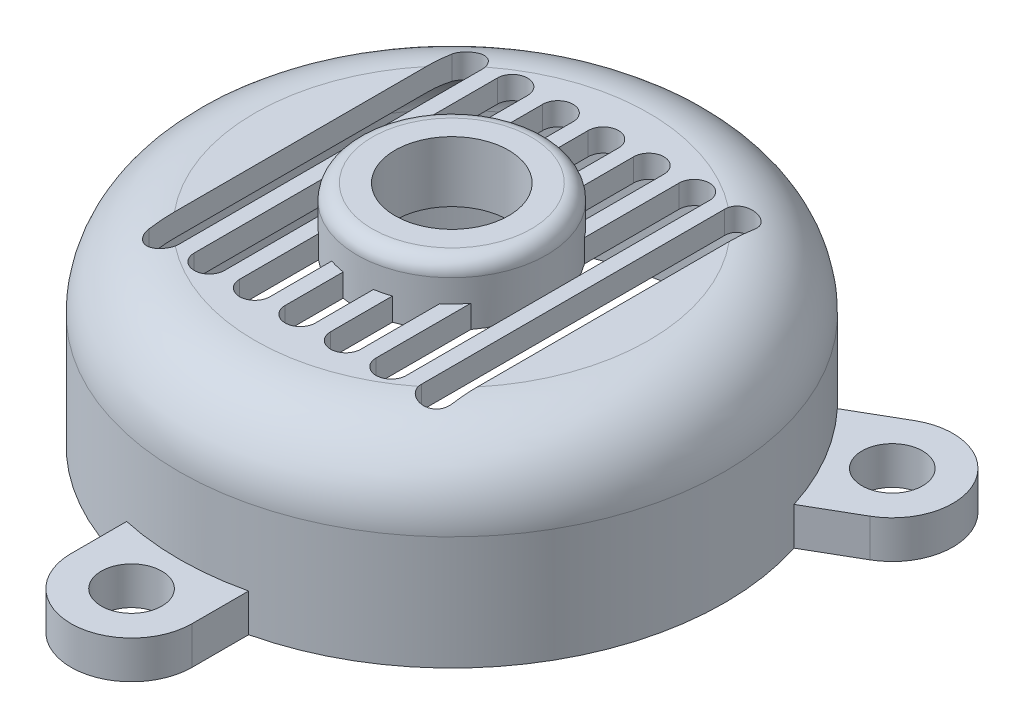
SolidWorks part; units mm, degrees
ref_plane "Front Plane" through (0, 0, 0) normal (0, 0, 1) x (1, 0, 0)
ref_plane "Top Plane" through (0, 0, 0) normal (0, 1, 0) x (1, 0, 0)
ref_plane "Right Plane" through (0, 0, 0) normal (1, 0, 0) x (0, 0, -1)
sketch "Sketch1" plane through (0, 0, 0) normal (0, 1, 0) x (1, 0, 0)
  circle A0 centre (0, 0) radius 36
  dimension "D1" = 72
extrude "Boss-Extrude1" add sketch "Sketch1" along normal blind 25
fillet "Fillet1" radius 10 1 edges at (0, 25, 36)
shell "Shell1" thickness 3 removed face at (0, 0, 36)
sketch "Sketch2" plane through (0, 0, 0) normal (0, -1, 0) x (1, 0, 0)
  line L5 (-7.7702, 33) -> (8.2298, 33)
  line L6 (-7.7702, 33) -> (-7.7702, 42.5)
  line L7 (-7.7702, 42.5) -> (8.2298, 42.5) construction
  line L8 (8.2298, 33) -> (8.2298, 42.5)
  line L9 (-7.7702, 33) -> (8.2298, 42.5) construction
  line L10 (-7.7702, 42.5) -> (8.2298, 33) construction
  arc A2 (8.2298, 42.5) -> (-7.7702, 42.5) centre (0.2298, 42.5) ccw
  circle A3 centre (0.2298, 42.5) radius 4
  circle A4 centre (0, 0) radius 33 construction
  point P0 (0.2298, 37.75)
  dimension "D1" = 16
  dimension "D2" = 8
  dimension "D3" = 42.5
extrude "Boss-Extrude2" add sketch "Sketch2" against normal blind 5
pattern_circular "CirPattern1" count 3 over 360 about axis through (0, 25, 0) along (0, -1, 0) of "Boss-Extrude2" reverse direction yes
sketch "Sketch3" plane through (0, 25, 0) normal (0, 1, 0) x (1, 0, 0)
  line L0 (-18, 20) -> (-18, -20) construction
  line L1 (-16, 20) -> (-16, -20)
  line L2 (-20, 20) -> (-20, -20)
  arc A0 (-16, 20) -> (-20, 20) centre (-18, 20) ccw
  arc A1 (-20, -20) -> (-16, -20) centre (-18, -20) ccw
  point P2 (-18, 0)
  point P7 (0, 0)
  dimension "D1" = 4
  dimension "D2" = 40
  dimension "D3" = 18
extrude "Cut-Extrude2" cut sketch "Sketch3" against normal through all
sketch "Sketch4" plane through (0, 25, 0) normal (0, 1, 0) x (1, 0, 0)
  line L0 (5.3515, 0) -> (21.8072, 0)
pattern_linear "LPattern1" count 7 spacing 6 along (1, 0, 0) of "Cut-Extrude2"
sketch "Sketch5" plane through (0, 25, 0) normal (0, 1, 0) x (1, 0, 0)
  circle A0 centre (0, 0) radius 12.5
  dimension "D1" = 25
extrude "Boss-Extrude3" add sketch "Sketch5" along normal blind 5 and the other way blind 3
fillet "Fillet2" radius 2 1 edges at (0, 30, 12.5)
sketch "Sketch6" plane through (0, 30, 0) normal (0, 1, 0) x (1, 0, 0)
  circle A0 centre (0, 0) radius 7.5
  dimension "D1" = 15
extrude "Cut-Extrude3" cut sketch "Sketch6" against normal through all
